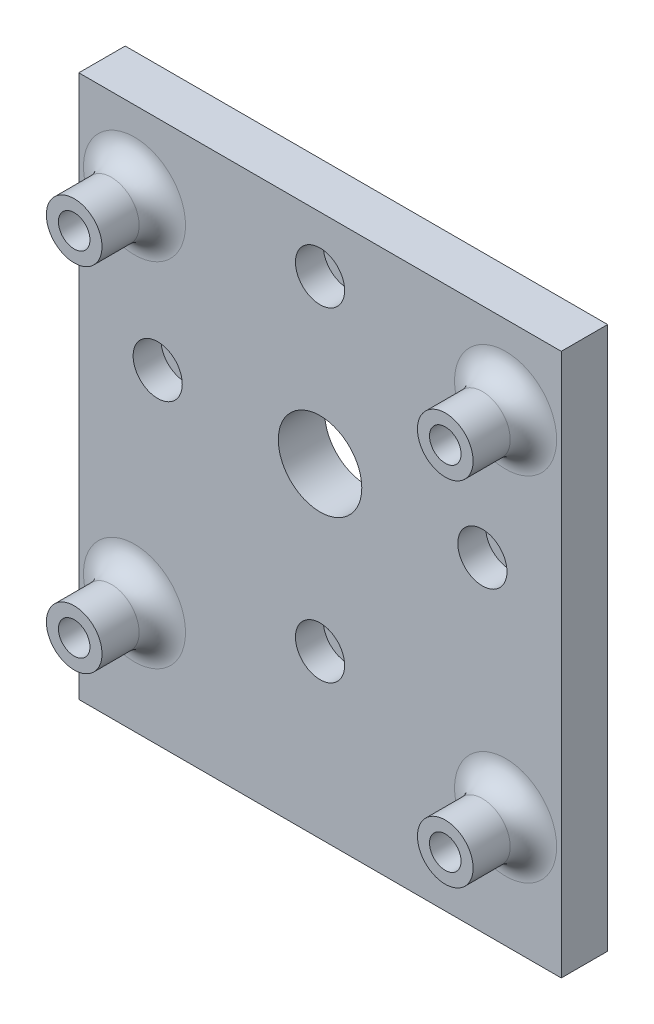
SolidWorks part; units mm, degrees
ref_plane "Front Plane" through (0, 0, 0) normal (0, 0, 1) x (1, 0, 0)
ref_plane "Top Plane" through (0, 0, 0) normal (0, 1, 0) x (1, 0, 0)
ref_plane "Right Plane" through (0, 0, 0) normal (1, 0, 0) x (0, 0, -1)
sketch "Sketch1" plane through (0, 0, 0) normal (0, 0, 1) x (1, 0, 0)
  line L0 (-20, 15) -> (20, 15) construction
  line L1 (-20, -23) -> (20, -23) construction
  line L2 (-20, 18) -> (20, 18)
  line L3 (-16, -35) -> (16, -35)
  line L4 (-23, 15) -> (-23, -23)
  line L5 (23, 15) -> (23, -23)
  line L6 (-27.3518, -23) -> (-27.3518, -29) construction
  line L7 (-27.3518, -29) -> (-27.3518, -35) construction
  line L8 (-27.3518, -29) -> (32.2638, -29) construction
  line L9 (-27.3518, -35) -> (32.2638, -35) construction
  line L10 (-16, -35) -> (-16, -29)
  line L11 (16, -35) -> (16, -29)
  line L12 (-20.8734, -26.0636) -> (-17.0471, -27.4916)
  line L13 (0, 21.7483) -> (0, -55.2269) construction
  line L15 (20.8734, -26.0636) -> (17.0471, -27.4916)
  circle A0 centre (0, 0) radius 3.2
  circle A1 centre (20, 15) radius 1.25
  circle A2 centre (-20, 15) radius 1.25
  circle A3 centre (-20, -23) radius 1.25
  circle A4 centre (20, -23) radius 1.25
  arc A5 (-20, 18) -> (-23, 15) centre (-20, 15) ccw
  arc A6 (23, 15) -> (20, 18) centre (20, 15) ccw
  arc A8 (-16, -29) -> (-17.0471, -27.4916) centre (-17.61, -29) ccw
  arc A9 (16, -29) -> (17.0471, -27.4916) centre (17.61, -29) cw
  arc A11 (-23, -23) -> (-20.8734, -26.0636) centre (-19.73, -23) ccw
  arc A12 (23, -23) -> (20.8734, -26.0636) centre (19.73, -23) cw
  point P5 (0, 15)
  point P10 (0, -23)
  point P18 (0, -35)
  dimension "D1" = 15
  dimension "D3" = 2.5
  dimension "D4" = 2.5
  dimension "D7" = 2.5
  dimension "D8" = 2.5
  dimension "D11" = 6
  dimension "D9" = 6
  dimension "D12" = 6.4
  dimension "D15" = 3.27
  dimension "D16" = 1.61
  dimension "D2" = 40
  dimension "D5" = 40
  dimension "D6" = 23
  dimension "D10" = 32
  dimension "D13" = 6
  dimension "D14" = 6
  dimension "D17" = 7.3518
sketch "Sketch2" plane through (0, 0, 0) normal (0, 0, 1) x (1, 0, 0)
  line L1 (0, 21.7483) -> (0, -55.2269) construction
  line L2 (-26, -35) -> (26, -35)
  line L3 (-26, -35) -> (-26, 23.5)
  line L4 (-26, 23.5) -> (26, 23.5)
  line L5 (26, -35) -> (26, 23.5)
  line L6 (-26, -35) -> (26, 23.5) construction
  line L7 (-26, 23.5) -> (26, -35) construction
  circle A0 centre (0, 0) radius 17.5 construction
  circle A1 centre (0, 17.5) radius 1.5
  circle A2 centre (17.5, 0) radius 1.5
  circle A3 centre (0, -17.5) radius 1.5
  circle A4 centre (-17.5, 0) radius 1.5
  circle A5 centre (0, 17.5) radius 2.65
  circle A6 centre (17.5, 0) radius 2.65
  circle A7 centre (0, -17.5) radius 2.65
  circle A8 centre (-17.5, 0) radius 2.65
  circle A9 centre (-20, -23) radius 1.25 construction
  circle A10 centre (20, -23) radius 1.25 construction
  circle A11 centre (20, 15) radius 1.25 construction
  circle A12 centre (-20, 15) radius 1.25 construction
  circle A13 centre (-20, -23) radius 1.25 construction
  circle A14 centre (20, -23) radius 1.25 construction
  circle A15 centre (20, 15) radius 1.25 construction
  circle A16 centre (-20, 15) radius 1.25 construction
  circle A17 centre (-20, 15) radius 1.7
  circle A18 centre (20, 15) radius 1.7
  circle A19 centre (20, -23) radius 1.7
  circle A20 centre (-20, -23) radius 1.7
  point P14 (0, 0)
  point P22 (0, 0)
  point P35 (0, -5.75)
  dimension "D1" = 35
  dimension "D2" = 3
  dimension "D4" = 5.3
  dimension "D6" = 3.4
  dimension "D7" = 3.4
  dimension "D8" = 3.4
  dimension "D9" = 3.4
  dimension "D10" = 6
  dimension "D11" = 6
  dimension "D12" = 12
  dimension "D3" = 4
  dimension "D5" = 4
extrude "Boss-Extrude1" add sketch "Sketch2" along normal blind 5 contours L2 L5 L4 L3 A20 A19 A18 A17 A8 A7 A6 A5 region at (0, -5.9457, 0)
extrude "Boss-Extrude2" add sketch "Sketch2<3>" along normal blind 2 contours A5 A1 | A8 A4 | A6 A2 | A7 A3 region at (-2.575, 17.5, 0) region at (14.925, 0, 0) region at (-2.575, -17.5, 0) region at (-20.075, 0, 0)
sketch "Sketch2<3>" plane through (0, 0, 0) normal (0, 0, 1) x (1, 0, 0) same geometry as "Sketch2"
sketch "Sketch3" plane through (0, 0, 5) normal (0, 0, 1) x (1, 0, 0)
  circle A0 centre (-20, -23) radius 1.7 construction
  circle A1 centre (20, -23) radius 1.7 construction
  circle A2 centre (20, 15) radius 1.7 construction
  circle A3 centre (-20, 15) radius 1.7 construction
  circle A4 centre (-20, -23) radius 1.7
  circle A5 centre (20, -23) radius 1.7
  circle A6 centre (20, 15) radius 1.7
  circle A7 centre (-20, 15) radius 1.7
  circle A8 centre (-20, 15) radius 3
  circle A9 centre (20, 15) radius 3
  circle A10 centre (-20, -23) radius 3
  circle A11 centre (20, -23) radius 3
  dimension "D1" = 6
  dimension "D2" = 6
  dimension "D3" = 6
  dimension "D4" = 6
extrude "Boss-Extrude3" add sketch "Sketch3" along normal blind 6.5
sketch "Sketch4" plane through (0, 0, 5) normal (0, 0, 1) x (1, 0, 0)
  line L4 (-26, -35) -> (26, -35)
  line L5 (26, -35) -> (26, 23.5)
  line L6 (26, 23.5) -> (-26, 23.5)
  line L7 (-26, 23.5) -> (-26, -35)
  line L8 (-26, -35) -> (26, -35)
  line L9 (26, -35) -> (26, 23.5)
  line L10 (26, 23.5) -> (-26, 23.5)
  line L11 (-26, 23.5) -> (-26, -35)
  circle A0 centre (0, 0) radius 3.2 construction
  circle A1 centre (0, 0) radius 3.2
  circle A2 centre (0, 0) radius 4.5
  dimension "D2" = 9
  dimension "D1" = 0
extrude "Cut-Extrude1" cut sketch "Sketch4" against normal through all both and the other way through all contours A1 | A2 A1 region at (0, 0, 5) region at (-4.3727, 0, 5)
fillet "Fillet1" radius 2.5 4 edges at (23, -23, 5) (-17, -23, 5) (23, 15, 5) (-17, 15, 5)
